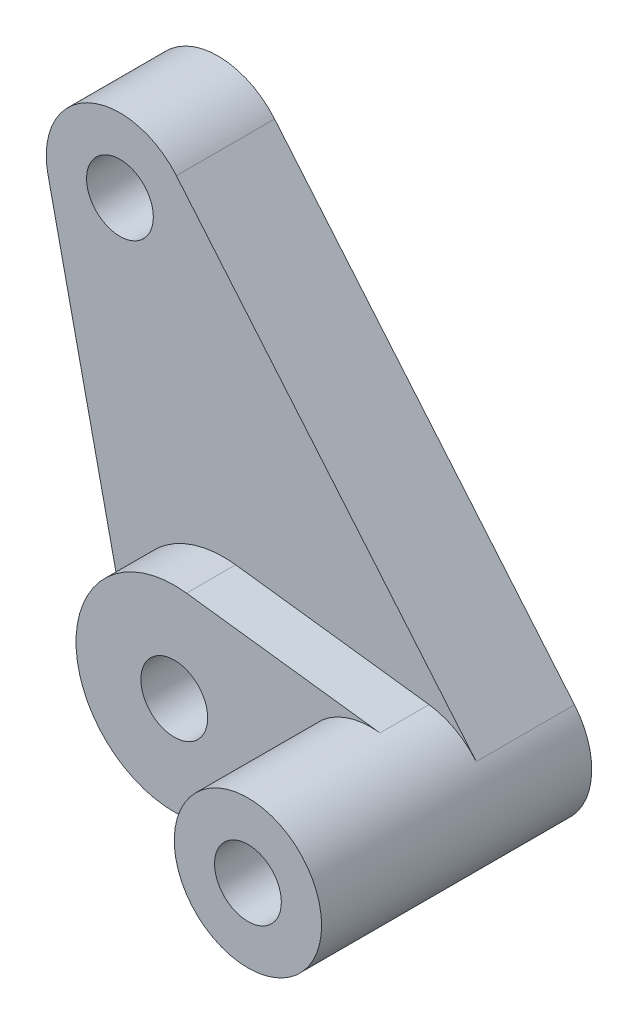
SolidWorks part; units mm, degrees
ref_plane "Front Plane" through (0, 0, 0) normal (0, 0, 1) x (1, 0, 0)
ref_plane "Top Plane" through (0, 0, 0) normal (0, 1, 0) x (1, 0, 0)
ref_plane "Right Plane" through (0, 0, 0) normal (1, 0, 0) x (0, 0, -1)
sketch "Sketch1" plane through (0, 0, 0) normal (0, 0, 1) x (1, 0, 0)
  line L0 (-12.7, 0) -> (0, 0) construction
  line L1 (0.5953, -4.7251) -> (-11.9062, -6.3002)
  line L3 (-19.3881, 23.1058) -> (0, 0) construction
  line L5 (3.6483, 3.0613) -> (-15.7398, 26.1671)
  line L6 (-24.0402, 22.0864) -> (-18.9028, -1.3592)
  line L7 (0, 0) -> (-19.3881, 23.1058) construction
  arc A0 (0.5953, -4.7251) -> (3.6483, 3.0613) centre (0, 0) ccw
  arc A1 (-18.9028, -1.3592) -> (-11.9062, -6.3002) centre (-12.7, 0) ccw
  arc A3 (-15.7398, 26.1671) -> (-24.0402, 22.0864) centre (-19.3881, 23.1058) ccw
  circle A4 centre (-12.7, 0) radius 2.159
  circle A5 centre (-19.3881, 23.1058) radius 2.159
  circle A6 centre (0, 0) radius 2.159
  dimension "D3" = 4.318
  dimension "D4" = 4.7625
  dimension "D5" = 6.35
  dimension "D6" = 4.7625
  dimension "D1" = 12.7
  dimension "D2" = 30.1625
  dimension "D7" = 50
extrude "Boss-Extrude1" add sketch "Sketch1" along normal mid plane 6.35
sketch "Sketch3" plane through (0, 0, 3.175) normal (0, 0, 1) x (1, 0, 0)
  circle A0 centre (0, 0) radius 4.7625
  circle A1 centre (0, 0) radius 2.159 construction
  circle A2 centre (0, 0) radius 2.159
extrude "Boss-Extrude2" add sketch "Sketch3" along normal blind 11.1125
sketch "Sketch4" plane through (0, 0, -3.175) normal (0, 0, -1) x (-1, 0, 0)
  line L1 (12.7, 5.1326) -> (8.255, 2.5663)
  line L2 (8.255, 2.5663) -> (8.255, -2.5663)
  line L3 (8.255, -2.5663) -> (12.7, -5.1326)
  line L4 (12.7, -5.1326) -> (17.145, -2.5663)
  line L5 (17.145, -2.5663) -> (17.145, 2.5663)
  line L6 (17.145, 2.5663) -> (12.7, 5.1326)
  circle A0 centre (12.7, 0) radius 4.445 construction
  dimension "D1" = 8.89
extrude "Cut-Extrude1" cut sketch "Sketch4" against normal blind 3.175
sketch "Sketch5" plane through (0, 0, 3.175) normal (0, 0, 1) x (1, 0, 0)
  line L0 (-11.9062, 6.3002) -> (0.5953, 4.7251)
  line L1 (-11.9062, -6.3002) -> (0.5953, -4.7251) construction
  line L2 (-11.9062, -6.3002) -> (0.5953, -4.7251)
  arc A0 (-11.9062, 6.3002) -> (-11.9062, -6.3002) centre (-12.7, 0) ccw
  circle A1 centre (0, 0) radius 4.7625 construction
  arc A2 (0.5953, 4.7251) -> (0.5953, -4.7251) centre (0, 0) ccw
  arc A3 (-18.9028, -1.3592) -> (-11.9062, -6.3002) centre (-12.7, 0) ccw construction
  circle A4 centre (-12.7, 0) radius 2.159 construction
  circle A5 centre (-12.7, 0) radius 2.159
  point P10 (0, 0)
extrude "Boss-Extrude3" add sketch "Sketch5" along normal blind 3.175
